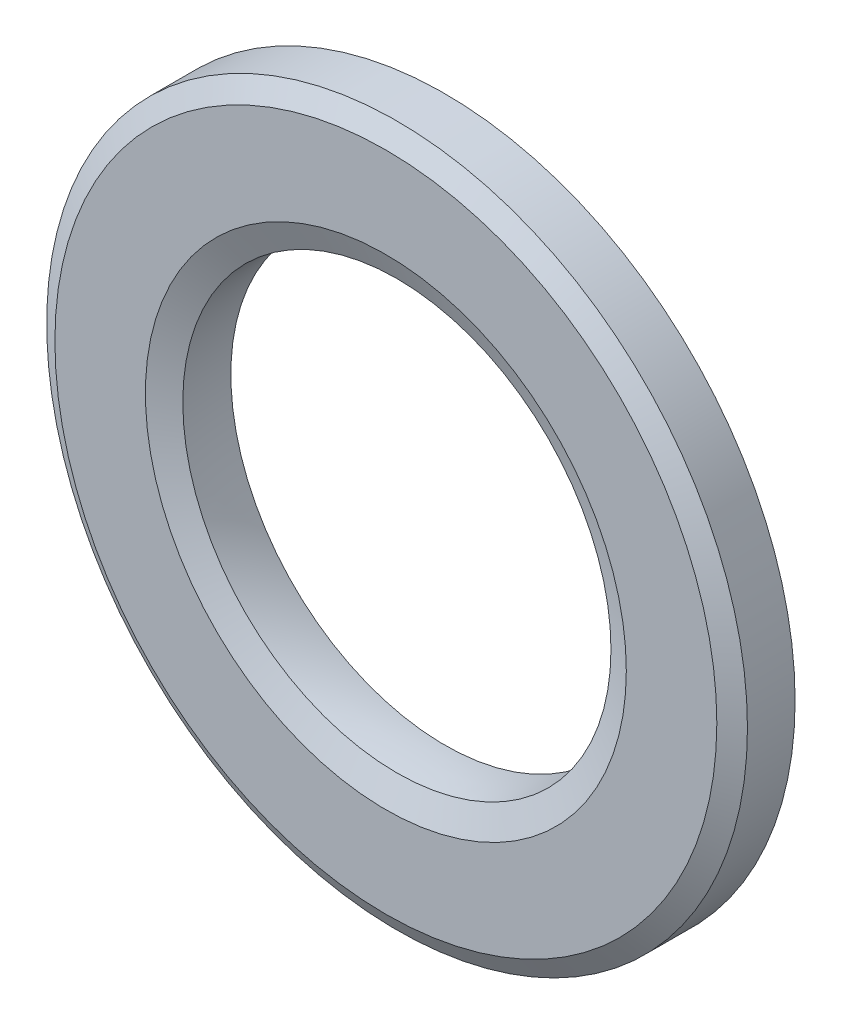
SolidWorks part; units mm, degrees
other "Imported1" parameters "D1"=0.254
material "Aluminum Bronze"
ref_plane "Front Plane" through (0, 0, 0) normal (0, 0, 1) x (1, 0, 0)
ref_plane "Top Plane" through (0, 0, 0) normal (0, 1, 0) x (1, 0, 0)
ref_plane "Right Plane" through (0, 0, 0) normal (1, 0, 0) x (0, 0, -1)
sketch "Sketch1" plane through (0, 0, 0) normal (0, 0, 1) x (1, 0, 0)
  line L0 (-7.9375, 0) -> (7.9375, 0) construction
  line L1 (-4.826, 0) -> (4.826, 0) construction
  circle A0 centre (0, 0) radius 4.826 construction
  circle A1 centre (0, 0) radius 7.9375 construction
  point P8 (0, 0)
  point P9 (0, 7.9375)
  point P11 (4.826, 0)
  dimension "ID" = 9.652
  dimension "OD" = 15.875
sketch "Sketch2" plane through (0, 0, 0) normal (1, 0, 0) x (0, 0, -1)
  line L0 (-0.7937, 7.9375) -> (0.7938, 7.9375) construction
  point P2 (0, 7.9375)
  dimension "Thickness" = 1.5875
sketch "Sketch3" plane through (0, 0, 0) normal (0, 0, 1) x (1, 0, 0)
  circle A0 centre (0, 0) radius 4.826
  circle A1 centre (0, 0) radius 7.9375
extrude "Boss-Extrude1" add sketch "Sketch3" along normal up to vertex (0.7937 mm away) and the other way up to vertex (0.7937 mm away) up to point (0, 7.9375, 0.7937) other way up to point (0, 7.9375, -0.7938)
chamfer "Chamfer1" distance 0.254 angle 60 2 edges at (7.9375, 0, -0.7938) (7.9375, 0, 0.7937)
sketch "Sketch4" plane through (0, 0, 0) normal (1, 0, 0) x (0, 0, -1)
  line L3 (-0.7937, 4.7752) -> (-0.7937, 4.8768)
  line L4 (-0.7937, 4.7752) -> (0.7938, 4.7752)
  line L5 (0.7938, 4.7752) -> (0.7938, 4.8768)
  line L6 (-0.7937, 0) -> (0.7937, 0) construction
  arc A0 (-0.7937, 4.8768) -> (0.7938, 4.8768) centre (0, 11.0526) ccw
  point P0 (0, 4.826)
  point P9 (-0.7937, 4.826)
  point P13 (0, 0)
  dimension "D1" = 0.0508
revolve "Cut-Revolve1" cut sketch "Sketch4" angle 360 about L6
chamfer "Chamfer2" distance 0.254 angle 60 2 edges at (0, -4.8768, -0.7938) (0, -4.8768, 0.7937)
equation "\"D1@Chamfer2\"=\"D1@Chamfer1\""
